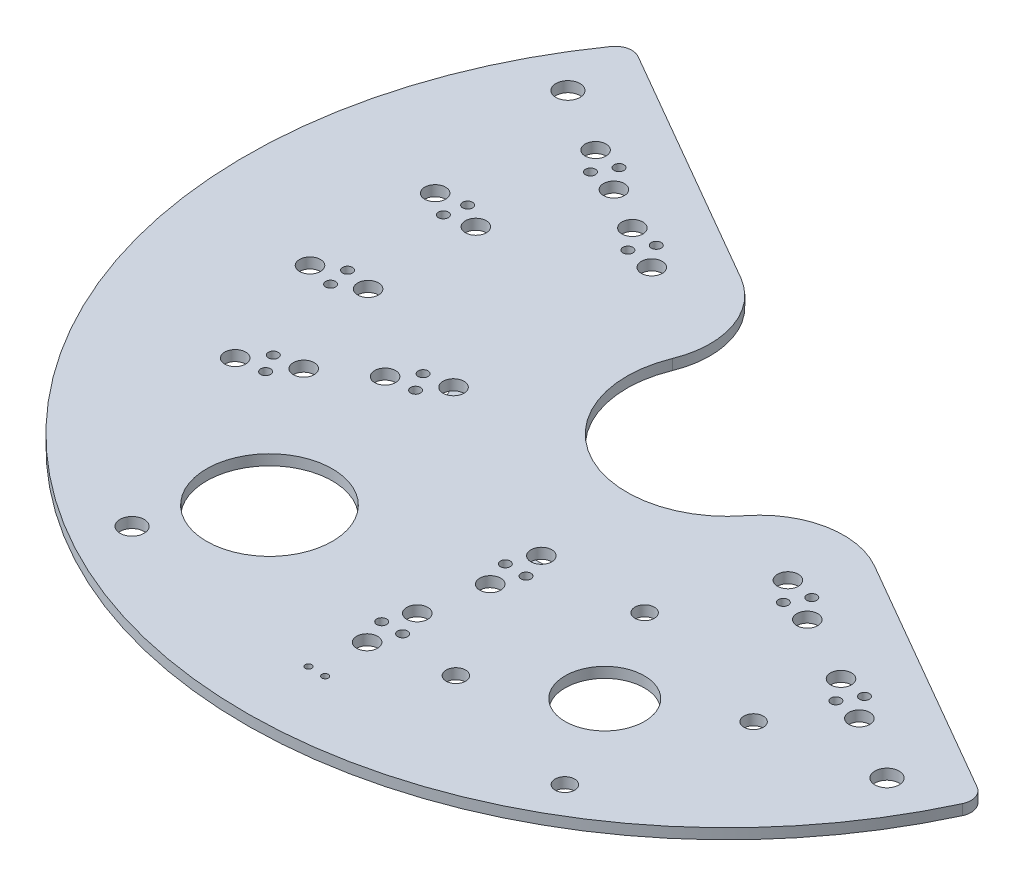
SolidWorks part; units mm, degrees
ref_plane "Front Plane" through (0, 0, 0) normal (0, 0, 1) x (1, 0, 0)
ref_plane "Top Plane" through (0, 0, 0) normal (0, 1, 0) x (1, 0, 0)
ref_plane "Right Plane" through (0, 0, 0) normal (1, 0, 0) x (0, 0, -1)
sketch "Sketch1" plane through (0, 0, 0) normal (0, 1, 0) x (1, 0, 0)
  line L0 (0, 50.8) -> (0, 59.6199) construction
  line L1 (0, 50.8) -> (11.3081, 50.8) construction
  line L2 (0, 0) -> (0, 47) construction
  line L3 (0, 0) -> (-46.286, 8.1615) construction
  line L4 (0, 0) -> (0, 47) construction
  line L5 (0, 0) -> (-46.286, -8.1615) construction
  line L6 (-30.1951, -16.4814) -> (-38.7564, -18.616) construction
  line L7 (1.7716, -33.8648) -> (4.3514, -25.4269) construction
  line L8 (26.6055, -18.425) -> (20.3665, -12.186) construction
  line L9 (-31.3367, 16.7365) -> (-37.5758, 22.9756) construction
  circle A0 centre (0, 0) radius 50.8 construction
  circle A1 centre (0, 0) radius 15.24
  circle A2 centre (0, 0) radius 73.025
  circle A3 centre (0, 50.8) radius 6.3 construction
  circle A4 centre (25.4, 43.9941) radius 6.3 construction
  circle A5 centre (43.9941, 25.4) radius 6.3 construction
  circle A6 centre (50.8, 0) radius 6.3 construction
  circle A7 centre (43.9941, -25.4) radius 6.3 construction
  circle A8 centre (25.4, -43.9941) radius 6.3 construction
  circle A9 centre (0, -50.8) radius 6.3 construction
  circle A10 centre (-25.4, -43.9941) radius 6.3 construction
  circle A11 centre (-43.9941, -25.4) radius 6.3 construction
  circle A12 centre (-50.8, 0) radius 6.3 construction
  circle A13 centre (-43.9941, 25.4) radius 6.3 construction
  circle A14 centre (-25.4, 43.9941) radius 6.3 construction
  circle A15 centre (0, 50.8) radius 1.585 construction
  circle A16 centre (-1.585, 50.8) radius 0.75
  circle A17 centre (1.585, 50.8) radius 0.75
  circle A18 centre (0, 50.8) radius 3.8 construction
  circle A19 centre (0, 54.6) radius 1.585
  circle A20 centre (0, 47) radius 1.585
  circle A21 centre (47.285, 27.3) radius 1.585
  circle A22 centre (43.2016, 26.7727) radius 0.75
  circle A23 centre (44.7866, 24.0273) radius 0.75
  circle A24 centre (40.7032, 23.5) radius 1.585
  circle A25 centre (47.285, -27.3) radius 1.585
  circle A26 centre (44.7866, -24.0273) radius 0.75
  circle A27 centre (43.2016, -26.7727) radius 0.75
  circle A28 centre (40.7032, -23.5) radius 1.585
  circle A29 centre (0, -54.6) radius 1.585
  circle A30 centre (1.585, -50.8) radius 0.75
  circle A31 centre (-1.585, -50.8) radius 0.75
  circle A32 centre (0, -47) radius 1.585
  circle A33 centre (-47.285, -27.3) radius 1.585
  circle A34 centre (-43.2016, -26.7727) radius 0.75
  circle A35 centre (-44.7866, -24.0273) radius 0.75
  circle A36 centre (-40.7032, -23.5) radius 1.585
  circle A37 centre (-47.285, 27.3) radius 1.585
  circle A38 centre (-44.7866, 24.0273) radius 0.75
  circle A39 centre (-43.2016, 26.7727) radius 0.75
  circle A40 centre (-40.7032, 23.5) radius 1.585
  circle A41 centre (25.4, 43.9941) radius 20
  circle A42 centre (-25.4, -43.9941) radius 9.525
  circle A43 centre (25.4, -43.9941) radius 6
  circle A44 centre (-46.286, 8.1615) radius 1.585
  circle A45 centre (-50.3035, 7.2604) radius 0.75
  circle A46 centre (-49.753, 10.3822) radius 0.75
  circle A47 centre (-53.7705, 9.4812) radius 1.585
  circle A48 centre (-46.286, -8.1615) radius 1.585
  circle A49 centre (-49.753, -10.3822) radius 0.75
  circle A50 centre (-50.3035, -7.2604) radius 0.75
  circle A51 centre (-53.7705, -9.4812) radius 1.585
  circle A52 centre (-30.191, -16.4817) radius 6.3 construction
  circle A53 centre (-30.191, -16.4817) radius 1.585 construction
  circle A54 centre (-29.3973, -17.8553) radius 0.75
  circle A55 centre (-31.002, -15.1168) radius 0.75
  circle A56 centre (-30.191, -16.4817) radius 3.8 construction
  circle A57 centre (-33.5032, -18.378) radius 1.585
  circle A58 centre (-26.9143, -14.5903) radius 1.585
  circle A59 centre (1.7693, -33.8681) radius 6.3 construction
  circle A60 centre (1.7693, -33.8681) radius 1.585 construction
  circle A61 centre (0.1831, -33.841) radius 0.75
  circle A62 centre (3.3569, -33.8759) radius 0.75
  circle A63 centre (1.7693, -33.8681) radius 3.8 construction
  circle A64 centre (1.8498, -30.0524) radius 1.585
  circle A65 centre (1.7028, -37.651) radius 1.585
  circle A66 centre (27.0699, -16.4457) radius 6.3 construction
  circle A67 centre (27.0699, -16.4457) radius 1.585 construction
  circle A68 centre (26.3013, -17.8335) radius 0.75
  circle A69 centre (27.8221, -15.0476) radius 0.75
  circle A70 centre (27.0699, -16.4457) radius 3.8 construction
  circle A71 centre (23.7386, -14.5832) radius 1.585
  circle A72 centre (30.3788, -18.2803) radius 1.585
  circle A73 centre (-30.934, 17.997) radius 6.3 construction
  circle A74 centre (-30.934, 17.997) radius 1.585 construction
  circle A75 centre (-31.7026, 16.6092) radius 0.75
  circle A76 centre (-30.1818, 19.3951) radius 0.75
  circle A77 centre (-30.934, 17.997) radius 3.8 construction
  circle A78 centre (-34.2653, 19.8594) radius 1.585
  circle A79 centre (-27.6251, 16.1623) radius 1.585
  point P50 (0, 0)
  point P84 (0, 0)
  dimension "D1" = 12
  dimension "D2" = 101.6
  dimension "D3" = 3.17
  dimension "D4" = 1.5
  dimension "D5" = 7.6
  dimension "D6" = 6
  dimension "D7" = 3.17
  dimension "D8" = 40
  dimension "D9" = 19.05
  dimension "D10" = 12
  dimension "D11" = 146.05
  dimension "D12" = 30.48
  dimension "D14" = 80
  dimension "D16" = 100
  dimension "D13" = 2
  dimension "D15" = 2
extrude "Boss-Extrude1" add sketch "Sketch1" against normal blind 1.5875
sketch "Sketch2" plane through (0, 0, 0) normal (0, 1, 0) x (1, 0, 0)
  line L0 (0, 0) -> (0, 66.04) construction
  line L1 (0, 0) -> (-57.1923, 33.02) construction
  circle A0 centre (0, 0) radius 66.04 construction
  circle A1 centre (0, 66.04) radius 1.8288 construction
  circle A2 centre (-57.1923, 33.02) radius 1.8288
  circle A3 centre (33.02, 57.1923) radius 1.8288
  circle A4 centre (57.1923, -33.02) radius 1.8288
  circle A5 centre (-33.02, -57.1923) radius 1.8288
  point P17 (0, 0)
  dimension "D1" = 132.08
  dimension "D2" = 3.6576
  dimension "D3" = 2
  dimension "D4" = 60
  dimension "D5" = 4
extrude "Cut-Extrude1" cut sketch "Sketch2" against normal through all
sketch "Sketch3" plane through (0, 0, 0) normal (0, 1, 0) x (1, 0, 0)
  line L0 (-57.1923, 33.02) -> (57.1923, -33.02) construction
  line L1 (-59.5338, 44.6372) -> (68.4238, -29.2392)
  line L2 (-52.7473, 40.719) -> (61.6373, -25.321) construction
  arc A0 (68.4238, -29.2392) -> (-59.5338, 44.6372) centre (0, 0) ccw
  dimension "D1" = 8.89
extrude "Cut-Extrude2" cut sketch "Sketch3" against normal through all
fillet "Fillet1" radius 12.7 2 edges at (15.165, -0.7937, -1.5098) (-6.275, -0.7937, -13.8882)
fillet "Fillet2" radius 2.54 2 edges at (67.2161, -0.7937, 28.542) (-58.3261, -0.7937, -43.9399)
sketch "Sketch4" plane through (0, 0, 0) normal (0, 1, 0) x (1, 0, 0)
  line L0 (0, 0) -> (0, -73.025) construction
  arc A0 (-59.6949, 42.0615) -> (66.2738, -30.6666) centre (0, 0) ccw construction
  circle A1 centre (0, 0) radius 62.23 construction
  circle A2 centre (0, -62.23) radius 0.4953 construction
  circle A3 centre (1.27, -62.23) radius 0.4953
  circle A4 centre (-1.27, -62.23) radius 0.4953
  dimension "D1" = 0.9906
  dimension "D4" = 124.46
  dimension "D2" = 2
  dimension "D3" = 2
extrude "Cut-Extrude3" cut sketch "Sketch4" against normal through all
sketch "Sketch5" plane through (0, -1.5875, 0) normal (0, -1, 0) x (1, 0, 0)
  line L13 (30.4135, 24.5983) -> (41.5359, 31.0198)
  line L14 (28.0125, 9.134) -> (57.7422, 26.2984)
  line L29 (46.7892, 22.3211) -> (54.7743, 26.9312)
  line L30 (29.0803, 12.0968) -> (45.0238, 21.3018)
  line L31 (6.096, 38.6381) -> (6.096, 51.4811)
  line L32 (29.8903, 21.9498) -> (40.9598, 28.3409)
  line L33 (-6.096, 38.6381) -> (-6.096, 51.4811)
  line L34 (4.064, 36.8606) -> (4.064, 49.6426)
  line L35 (-21.9165, -19.6925) -> (-41.5359, -31.0198)
  line L39 (-4.064, 36.8606) -> (-4.064, 49.6426)
  line L40 (-30.4135, 24.5983) -> (-41.5359, 31.0198)
  line L42 (-29.8903, 21.9498) -> (-40.9598, 28.3409)
  line L93 (-25.0163, -19.1359) -> (-40.9598, -28.3409)
  arc A0 (1.2946, 63.4357) -> (1.2454, 61.0243) centre (1.27, 62.23) ccw
  arc A1 (-1.1373, 61.0264) -> (-1.1844, 63.4379) centre (-1.27, 62.23) ccw
  arc A2 (-1.1373, 61.0264) -> (-54.0489, -28.3589) centre (0, 0) ccw
  arc A3 (-1.1844, 63.4379) -> (-56.1144, -29.6131) centre (0, 0) ccw
  arc A4 (54.7743, 26.9312) -> (1.2454, 61.0243) centre (0, 0) ccw
  arc A5 (-56.1144, -29.6131) -> (-54.0489, -28.3589) centre (-55.1689, -28.8424) ccw
  arc A6 (6.096, 51.4811) -> (2.3857, 51.7858) centre (0, 0) ccw
  arc A7 (29.8903, 21.9498) -> (4.064, 36.8606) centre (0, 0) ccw
  arc A8 (2.3857, 51.7858) -> (2.3071, 49.7553) centre (1.585, 50.8) ccw
  arc A9 (-2.3071, 49.7553) -> (-2.3857, 51.7858) centre (-1.585, 50.8) ccw
  arc A10 (-48.5987, -10.912) -> (-50.5848, -11.342) centre (-49.753, -10.3822) ccw
  arc A11 (-51.4133, -6.6431) -> (-49.4, -6.3679) centre (-50.3035, -7.2604) ccw
  arc A12 (46.0407, 23.8268) -> (44.2429, 22.8796) centre (44.7866, 24.0273) ccw
  arc A13 (41.9358, 26.8756) -> (43.655, 27.959) centre (43.2016, 26.7727) ccw
  arc A14 (-49.4, 6.3679) -> (-51.4133, 6.6431) centre (-50.3035, 7.2604) ccw
  arc A15 (-50.5848, 11.342) -> (-48.5987, 10.912) centre (-49.753, 10.3822) ccw
  arc A16 (57.7422, 26.2984) -> (1.2946, 63.4357) centre (0, 0) ccw
  arc A17 (-2.3857, 51.7858) -> (-6.096, 51.4811) centre (0, 0) ccw
  arc A18 (-2.3071, 49.7553) -> (-4.064, 49.6426) centre (0, 0) ccw
  arc A19 (45.0238, 21.3018) -> (44.2429, 22.8796) centre (0, 0) ccw
  arc A20 (29.0803, 12.0968) -> (-25.0163, -19.1359) centre (0, 0) ccw
  arc A21 (28.0125, 9.134) -> (-21.9165, -19.6925) centre (0, 0) ccw
  arc A22 (46.7892, 22.3211) -> (46.0407, 23.8268) centre (0, 0) ccw
  arc A23 (43.655, 27.959) -> (41.5359, 31.0198) centre (0, 0) ccw
  arc A24 (-46.0407, -23.8268) -> (-44.2429, -22.8796) centre (-44.7866, -24.0273) ccw
  arc A25 (-41.9358, -26.8756) -> (-43.655, -27.959) centre (-43.2016, -26.7727) ccw
  arc A26 (41.9358, 26.8756) -> (40.9598, 28.3409) centre (0, 0) ccw
  circle A27 centre (1.27, 62.23) radius 0.4953
  arc A28 (-43.655, 27.959) -> (-41.9358, 26.8756) centre (-43.2016, 26.7727) ccw
  arc A29 (-44.2429, 22.8796) -> (-46.0407, 23.8268) centre (-44.7866, 24.0273) ccw
  circle A30 centre (-1.27, 62.23) radius 0.4953
  arc A31 (-43.655, -27.959) -> (-41.5359, -31.0198) centre (0, 0) ccw
  circle A32 centre (-26.7727, 43.2016) radius 1.27 [skipped]
  circle A33 centre (-24.0273, 44.7866) radius 1.27 [skipped]
  circle A34 centre (24.0273, 44.7866) radius 1.27 [skipped]
  circle A35 centre (26.7727, 43.2016) radius 1.27 [skipped]
  circle A36 centre (50.8, 1.585) radius 1.27 [skipped]
  circle A37 centre (50.8, -1.585) radius 1.27 [skipped]
  circle A38 centre (44.7866, -24.0273) radius 1.27 [skipped]
  circle A39 centre (43.2016, -26.7727) radius 1.27 [skipped]
  circle A40 centre (26.7727, -43.2016) radius 1.27 [skipped]
  circle A41 centre (24.0273, -44.7866) radius 1.27 [skipped]
  circle A42 centre (1.585, -50.8) radius 1.27 [skipped]
  circle A43 centre (-1.585, -50.8) radius 1.27 [skipped]
  circle A44 centre (-24.0273, -44.7866) radius 1.27 [skipped]
  circle A45 centre (-26.7727, -43.2016) radius 1.27 [skipped]
  circle A46 centre (-50.8, 1.585) radius 1.27 [skipped]
  circle A47 centre (-50.8, -1.585) radius 1.27 [skipped]
  arc A48 (-41.9358, -26.8756) -> (-40.9598, -28.3409) centre (0, 0) ccw
  arc A49 (-40.9598, 28.3409) -> (-41.9358, 26.8756) centre (0, 0) ccw
  arc A50 (30.4135, 24.5983) -> (6.096, 38.6381) centre (0, 0) ccw
  circle A51 centre (1.585, 50.8) radius 0.75
  arc A52 (-46.0407, 23.8268) -> (-47.6319, 20.4612) centre (0, 0) ccw
  arc A53 (4.064, 49.6426) -> (2.3071, 49.7553) centre (0, 0) ccw
  arc A54 (-41.5359, 31.0198) -> (-43.655, 27.959) centre (0, 0) ccw
  arc A55 (-6.096, 38.6381) -> (-30.4135, 24.5983) centre (0, 0) ccw
  arc A56 (-4.064, 36.8606) -> (-29.8903, 21.9498) centre (0, 0) ccw
  arc A57 (-44.2429, 22.8796) -> (-48.5987, 10.912) centre (0, 0) ccw
  circle A58 centre (-1.585, 50.8) radius 0.75
  circle A59 centre (43.2016, 26.7727) radius 0.75
  arc A60 (-47.6319, 20.4612) -> (-50.5848, 11.342) centre (0, 0) ccw
  arc A61 (-51.4133, 6.6431) -> (-51.4133, -6.6431) centre (0, 0) ccw
  arc A62 (-49.4, 6.3679) -> (-49.4, -6.3679) centre (0, 0) ccw
  circle A63 centre (44.7866, 24.0273) radius 0.75
  arc A64 (-50.5848, -11.342) -> (-46.0407, -23.8268) centre (0, 0) ccw
  arc A65 (-48.5987, -10.912) -> (-44.2429, -22.8796) centre (0, 0) ccw
  circle A66 centre (-43.2016, 26.7727) radius 0.75
  circle A67 centre (-44.7866, 24.0273) radius 0.75
  circle A68 centre (-49.753, 10.3822) radius 0.75
  circle A69 centre (-50.3035, 7.2604) radius 0.75
  circle A70 centre (-50.3035, -7.2604) radius 0.75
  circle A71 centre (-49.753, -10.3822) radius 0.75
  circle A72 centre (-44.7866, -24.0273) radius 0.75
  circle A73 centre (-43.2016, -26.7727) radius 0.75
  point P35 (0, 0)
  point P41 (0, 0)
  point P42 (-54.2332, -28.0055)
  point P45 (-55.1689, -28.8424)
  point P50 (0, 0)
  point P51 (0, 0)
  point P52 (0, 0)
  point P53 (0, 0)
  point P54 (0, 0)
  dimension "D13" = 12
  dimension "D15" = 3
extrude "Boss-Extrude2" add sketch "Sketch5" along normal blind 0.1016
sketch "Sketch6" plane through (0, -1.5875, 0) normal (0, -1, 0) x (1, 0, 0)
  line L0 (0, 0) -> (25.4, 43.9941) construction
  line L1 (25.4, 43.9941) -> (36.5125, 63.2415) construction
  circle A0 centre (25.4, 43.9941) radius 16.51 construction
  arc A1 (66.2738, 30.6666) -> (-59.6949, -42.0615) centre (0, 0) ccw construction
  circle A2 centre (33.655, 58.2922) radius 1.4732
  circle A3 centre (11.1019, 52.2491) radius 1.4732
  circle A4 centre (17.145, 29.696) radius 1.4732
  circle A5 centre (39.6981, 35.7391) radius 1.4732
  point P20 (25.4, 43.9941)
  dimension "D1" = 2.9464
extrude "Cut-Extrude4" cut sketch "Sketch6" against normal through all
